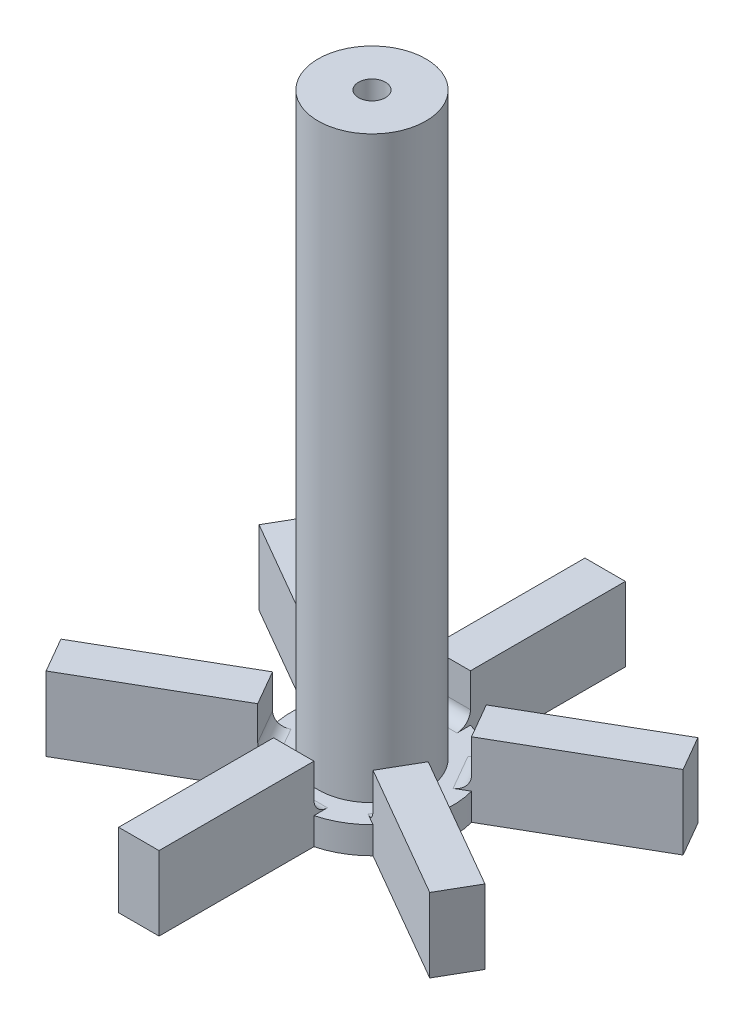
SolidWorks part; units mm, degrees
ref_plane "Front Plane" through (0, 0, 0) normal (0, 0, 1) x (1, 0, 0)
ref_plane "Top Plane" through (0, 0, 0) normal (0, 1, 0) x (1, 0, 0)
ref_plane "Right Plane" through (0, 0, 0) normal (1, 0, 0) x (0, 0, -1)
sketch "Sketch1" plane through (0, 0, 0) normal (0, 1, 0) x (1, 0, 0)
  line L48 (-1.5, -5.8095) -> (1.5, -5.8095)
  line L55 (1.5, -5.8095) -> (1.5, -17.3095)
  line L62 (1.5, -17.3095) -> (-1.5, -17.3095)
  line L69 (-1.5, -17.3095) -> (-1.5, -5.8095)
  line L70 (-15.7404, -7.3557) -> (-5.7812, -1.6057)
  line L71 (-5.7812, -1.6057) -> (-4.2812, -4.2038)
  line L72 (-4.2812, -4.2038) -> (-14.2404, -9.9538)
  line L73 (-14.2404, -9.9538) -> (-15.7404, -7.3557)
  line L74 (-14.2404, 9.9538) -> (-4.2812, 4.2038)
  line L75 (-4.2812, 4.2038) -> (-5.7812, 1.6057)
  line L76 (-5.7812, 1.6057) -> (-15.7404, 7.3557)
  line L77 (-15.7404, 7.3557) -> (-14.2404, 9.9538)
  line L78 (1.5, 17.3095) -> (1.5, 5.8095)
  line L79 (1.5, 5.8095) -> (-1.5, 5.8095)
  line L80 (-1.5, 5.8095) -> (-1.5, 17.3095)
  line L81 (-1.5, 17.3095) -> (1.5, 17.3095)
  line L82 (15.7404, 7.3557) -> (5.7812, 1.6057)
  line L83 (5.7812, 1.6057) -> (4.2812, 4.2038)
  line L84 (4.2812, 4.2038) -> (14.2404, 9.9538)
  line L85 (14.2404, 9.9538) -> (15.7404, 7.3557)
  line L86 (14.2404, -9.9538) -> (4.2812, -4.2038)
  line L87 (4.2812, -4.2038) -> (5.7812, -1.6057)
  line L88 (5.7812, -1.6057) -> (15.7404, -7.3557)
  line L89 (15.7404, -7.3557) -> (14.2404, -9.9538)
  circle A1 centre (0, 0) radius 1
  circle A2 centre (0, 0) radius 4
  arc A3 (1.5, -5.8095) -> (4.2812, -4.2038) centre (0, 0) ccw
  arc A4 (-4.2812, -4.2038) -> (-1.5, -5.8095) centre (0, 0) ccw
  arc A5 (-5.7812, 1.6057) -> (-5.7812, -1.6057) centre (0, 0) ccw
  arc A6 (-1.5, 5.8095) -> (-4.2812, 4.2038) centre (0, 0) ccw
  arc A7 (4.2812, 4.2038) -> (1.5, 5.8095) centre (0, 0) ccw
  arc A8 (5.7812, -1.6057) -> (5.7812, 1.6057) centre (0, 0) ccw
  point P9 (0, -5.8095)
  point P31 (0, 0)
  point P32 (0, 0)
  point P33 (0, 0)
  point P46 (0.0289, 0.0554)
  dimension "D1" = 2
  dimension "D2" = 8
  dimension "D3" = 2
  dimension "D4" = 3
  dimension "D5" = 11.5
  dimension "D6" = 6
extrude "Boss-Extrude1" add sketch "Sketch1" along normal blind 45 contours A1 region at (-3.8869, 0, 0)
extrude "Boss-Extrude2" add sketch "Sketch1<3>" along normal blind 5.5 contours L62 | L69 L48 L55 L62 | L70 L71 L72 L73 | L74 L75 L76 L77 | L78 L79 L80 L81 | L82 L83 L84 L85 | L86 L87 L88 L89
sketch "Sketch1<3>" plane through (0, 0, 0) normal (0, 1, 0) x (1, 0, 0) same geometry as "Sketch1"
extrude "Boss-Extrude3" add sketch "Sketch1<4>" along normal blind 2 contours L87 A8 L83 A7 L79 A6 L75 A5 L71 A4 L48 A3 A2 region at (-2.9165, 0, 5.0515)
sketch "Sketch1<4>" plane through (0, 0, 0) normal (0, 1, 0) x (1, 0, 0) same geometry as "Sketch1"
combine bodies "Combine1" operation type add bodies to combine 125 126 127 128 123 124 121
fillet "Fillet5" radius 1 6 edges at (-5.0312, 2, 2.9047) (0, 2, 5.8095) (5.0312, 2, 2.9047) (-5.0312, 2, -2.9047) (0, 2, -5.8095) (5.0312, 2, -2.9047)
